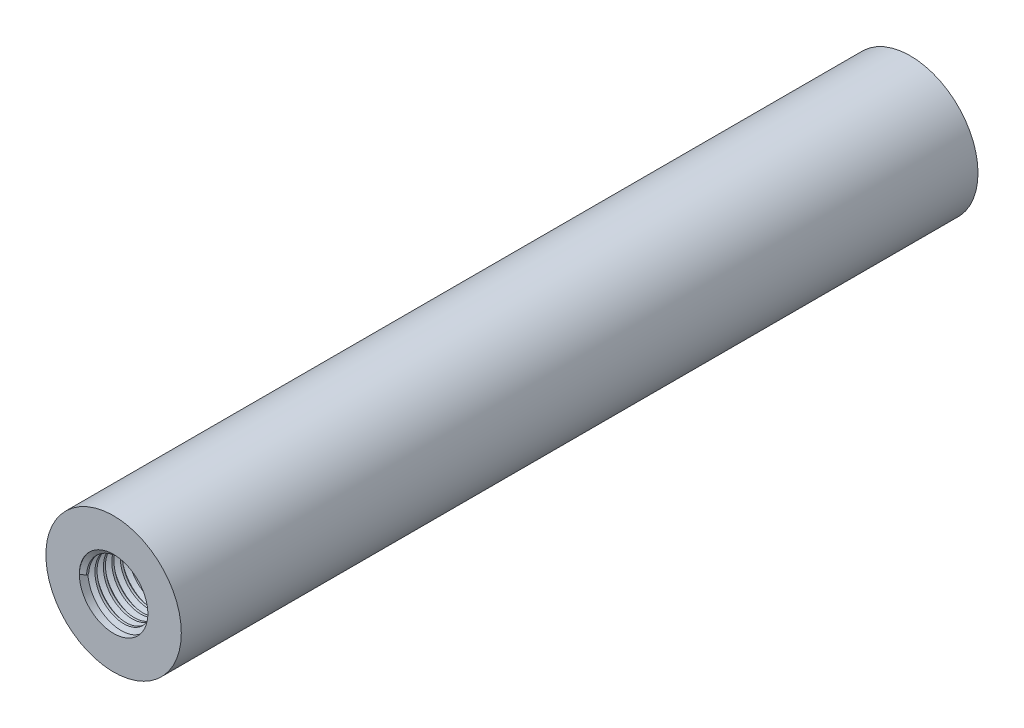
SolidWorks part; units mm, degrees
ref_plane "前视基准面" through (0, 0, 0) normal (0, 0, 1) x (1, 0, 0)
ref_plane "上视基准面" through (0, 0, 0) normal (0, 1, 0) x (1, 0, 0)
ref_plane "右视基准面" through (0, 0, 0) normal (1, 0, 0) x (0, 0, -1)
other "Configuration Table"
sketch "草图1" plane through (0, 0, 0) normal (0, 0, 1) x (1, 0, 0)
  circle A0 centre (0, 0) radius 2.55
  circle A1 centre (0, 0) radius 1.29
extrude "凸台-拉伸2" add sketch "草图1" along normal blind 30
thread "螺纹线1" pitch 0.3175 method extrude profile "螺纹线轮廓2" start angle 0, offset 0, length 10, pitch 0.3175, diameter 2.58
ref_plane "基准面2" through (1.29, 0, 0) normal (0, -1, 0) x (1, 0, 0)
sketch "螺纹线轮廓2" plane through (1.29, 0, 0) normal (0, -1, 0) x (1, 0, 0)
  line L0 (0, 0) -> (0, 0.3175) construction
  line L11 (0, 0) -> (0, 0.2778)
  line L12 (0, 0.2778) -> (-0.1719, 0.1786)
  line L13 (-0.1719, 0.1786) -> (-0.1719, 0.0992)
  line L15 (-0.1719, 0.0992) -> (0, 0)
  line L17 (-0.1719, 0.1389) -> (0, 0.1389) construction
  point P2 (0, 0)
  dimension "Pitch" = 0.3175
  dimension "Profile_Angle" = 60
  dimension "Profile_Land" = 0.0794
  dimension "Profile_Height" = 0.1719
thread "螺纹线2" pitch 0.3175 method extrude profile "螺纹线轮廓3" start angle 0, offset 0, length 10, pitch 0.3175, diameter 2.58
ref_plane "基准面3" through (-1.29, 0, 30) normal (0, -1, 0) x (-1, 0, 0)
sketch "螺纹线轮廓3" plane through (-1.29, 0, 30) normal (0, -1, 0) x (-1, 0, 0)
  line L0 (0, 0) -> (0, 0.3175) construction
  line L11 (0, 0) -> (0, 0.2778)
  line L12 (0, 0.2778) -> (-0.1719, 0.1786)
  line L13 (-0.1719, 0.1786) -> (-0.1719, 0.0992)
  line L15 (-0.1719, 0.0992) -> (0, 0)
  line L17 (-0.1719, 0.1389) -> (0, 0.1389) construction
  point P2 (0, 0)
  dimension "Pitch" = 0.3175
  dimension "Profile_Angle" = 60
  dimension "Profile_Land" = 0.0794
  dimension "Profile_Height" = 0.1719
